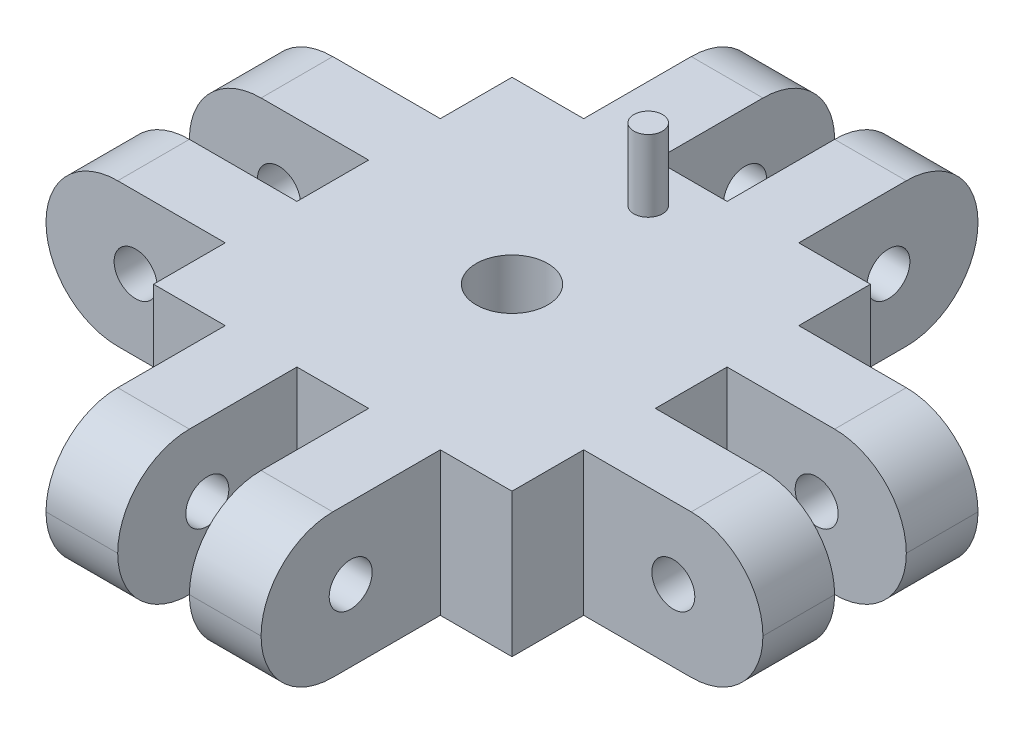
SolidWorks part; units mm, degrees
ref_plane "Front Plane" through (0, 0, 0) normal (0, 0, 1) x (1, 0, 0)
ref_plane "Top Plane" through (0, 0, 0) normal (0, 1, 0) x (1, 0, 0)
ref_plane "Right Plane" through (0, 0, 0) normal (1, 0, 0) x (0, 0, -1)
sketch "Sketch1" plane through (0, 0, 0) normal (0, 1, 0) x (1, 0, 0)
  line L0 (-7.5, 12.5) -> (-7.5, 25)
  line L1 (12.5, -12.5) -> (-12.5, -12.5)
  line L2 (12.5, -12.5) -> (12.5, 12.5)
  line L3 (12.5, 12.5) -> (-12.5, 12.5)
  line L4 (-12.5, -12.5) -> (-12.5, 12.5)
  line L5 (12.5, -12.5) -> (-12.5, 12.5) construction
  line L6 (12.5, 12.5) -> (-12.5, -12.5) construction
  line L7 (-7.5, 25) -> (-2.5, 25)
  line L8 (-2.5, 25) -> (-2.5, 12.5)
  line L9 (0, -1000) -> (0, 49000) construction
  line L10 (-1000, 0) -> (49000, 0) construction
  line L11 (2.5, 25) -> (2.5, 12.5)
  line L12 (7.5, 25) -> (2.5, 25)
  line L13 (7.5, 12.5) -> (7.5, 25)
  line L14 (7.5, -12.5) -> (7.5, -25)
  line L15 (7.5, -25) -> (2.5, -25)
  line L16 (2.5, -25) -> (2.5, -12.5)
  line L17 (-2.5, -25) -> (-2.5, -12.5)
  line L18 (-7.5, -25) -> (-2.5, -25)
  line L19 (-7.5, -12.5) -> (-7.5, -25)
  line L20 (12.5, 7.5) -> (25, 7.5)
  line L21 (25, 7.5) -> (25, 2.5)
  line L22 (25, 2.5) -> (12.5, 2.5)
  line L23 (12.5, -7.5) -> (25, -7.5)
  line L24 (25, -2.5) -> (12.5, -2.5)
  line L25 (25, -7.5) -> (25, -2.5)
  line L26 (-12.5, -7.5) -> (-25, -7.5)
  line L27 (-25, -7.5) -> (-25, -2.5)
  line L28 (-25, -2.5) -> (-12.5, -2.5)
  line L29 (-25, 2.5) -> (-12.5, 2.5)
  line L30 (-25, 7.5) -> (-25, 2.5)
  line L31 (-12.5, 7.5) -> (-25, 7.5)
  point P0 (0, 0)
  dimension "D1" = 25
  dimension "D2" = 12.5
  dimension "D3" = 5
  dimension "D4" = 5
  dimension "D5" = 12.5
  dimension "D6" = 5
  dimension "D7" = 5
extrude "Boss-Extrude1" add sketch "Sketch1" along normal blind 10 contours L4 L31 L30 L29 | L4 L1 L2 L3 | L8 L7 L0 L3 | L3 L13 L12 L11 | L22 L21 L20 L2 | L23 L25 L24 L2 | L16 L15 L14 L1 | L1 L19 L18 L17 | L28 L27 L26 L4 region at (-5, 0, -18.75) region at (0, 0, 0) region at (5, 0, -18.75) region at (-18.75, 0, -5) region at (-18.75, 0, 5) region at (18.75, 0, -5) region at (18.75, 0, 5) region at (-5, 0, 18.75) region at (5, 0, 18.75)
sketch "Sketch3" plane through (-7.5, 0, 0) normal (-1, 0, 0) x (0, 0, 1)
  line L0 (-12.5, 10) -> (-25, 10) construction
  line L1 (-25, 10) -> (-25, 0) construction
  circle A0 centre (-18.75, 5) radius 1.5
  point P5 (-18.75, 10)
  point P9 (-25, 5)
  dimension "D1" = 3
extrude "Cut-Extrude1" cut sketch "Sketch3" against normal through all
mirror "Mirror1" about plane through (0, 0, 0) normal (0, 0, 1) of "Cut-Extrude1"
sketch "Sketch4" plane through (0, 0, 7.5) normal (0, 0, 1) x (1, 0, 0)
  line L0 (-12.5, 10) -> (-25, 10) construction
  line L1 (-25, 10) -> (-25, 0) construction
  circle A0 centre (-18.75, 5) radius 1.5
  point P4 (-18.75, 10)
  point P8 (-25, 5)
  dimension "D1" = 3
extrude "Cut-Extrude2" cut sketch "Sketch4" against normal through all
mirror "Mirror2" about plane through (0, 0, 0) normal (1, 0, 0) of "Cut-Extrude2"
fillet "Fillet1" radius 5 16 edges at (-5, 0, -25) (-5, 10, -25) (5, 0, -25) (5, 10, -25) (25, 0, -5) (25, 10, -5) (25, 0, 5) (25, 10, 5) (5, 0, 25) (5, 10, 25) (-5, 0, 25) (-5, 10, 25) (-25, 10, 5) (-25, 0, 5) (-25, 0, -5) (-25, 10, -5)
sketch "Sketch5" plane through (0, 10, 0) normal (0, 1, 0) x (1, 0, 0)
  circle A0 centre (0, 0) radius 2.5
  dimension "D1" = 5
extrude "Cut-Extrude3" cut sketch "Sketch5" against normal blind 10
sketch "Sketch6" plane through (0, 10, 0) normal (0, 1, 0) x (1, 0, 0)
  line L0 (2.5, 12.5) -> (-2.5, 12.5) construction
  circle A0 centre (0, 9.5) radius 1
  point P4 (1.0864, 9.5)
  dimension "D1" = 2
  dimension "D2" = 3
extrude "Boss-Extrude2" add sketch "Sketch6" along normal blind 5
